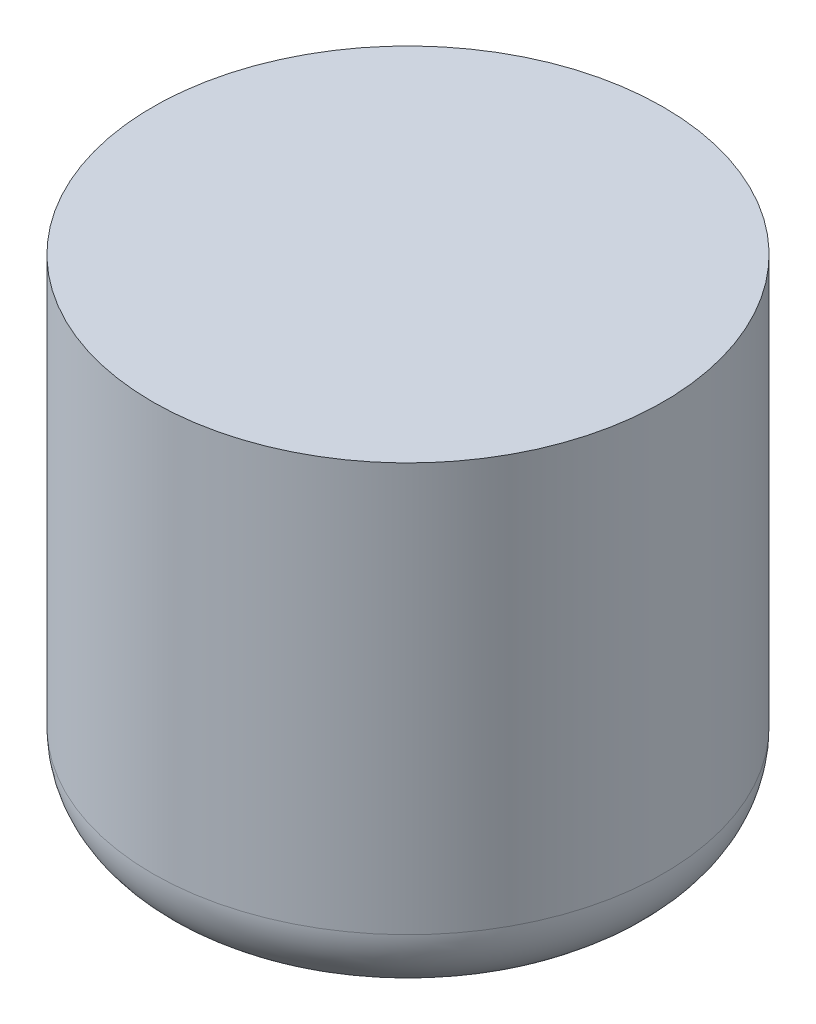
SolidWorks part; units mm, degrees
material "Water"
ref_plane "Front Plane" through (0, 0, 0) normal (0, 0, 1) x (1, 0, 0)
ref_plane "Top Plane" through (0, 0, 0) normal (0, 1, 0) x (1, 0, 0)
ref_plane "Right Plane" through (0, 0, 0) normal (1, 0, 0) x (0, 0, -1)
sketch "Sketch1" plane through (0, 0, 0) normal (0, 0, 1) x (1, 0, 0)
  line L0 (0, 170) -> (0, 770)
  line L1 (0, 770) -> (375, 770)
  line L2 (375, 770) -> (375, 170)
  line L3 (0, 170) -> (0, 0)
  line L4 (200, 31.3778) -> (200, 770) construction
  line L5 (200, 770) -> (200, 970) construction
  line L6 (200, 31.3778) -> (0, 31.3778) construction
  arc A2 (375, 170) -> (305, 70) centre (268.5714, 170) cw
  arc A3 (0, 0) -> (305, 70) centre (-22.9979, 799.6694) ccw
  dimension "D7" = 800
  dimension "D1" = 600
  dimension "D2" = 375
  dimension "D3" = 600
  dimension "D4" = 170
  dimension "D5" = 100
  dimension "D6" = 70
  dimension "D8" = 200
  dimension "D9" = 738.6222
  dimension "D10" = 200
  dimension "D11" = 70
  dimension "D12" = 100
  dimension "D13" = 600
revolve "Revolve1" add sketch "Sketch1" angle 360 about L0
ref_plane "Plane1" [suppressed] through (0, 170, 0) normal (0, 1, 0) x (1, 0, 0)
sketch "Sketch2" [suppressed] plane through (0, 170, 0) normal (0, 1, 0) x (1, 0, 0)
  circle A0 centre (0, 0) radius 672.1242
extrude "Cut-Extrude1" [suppressed] cut sketch "Sketch2" along normal through all
